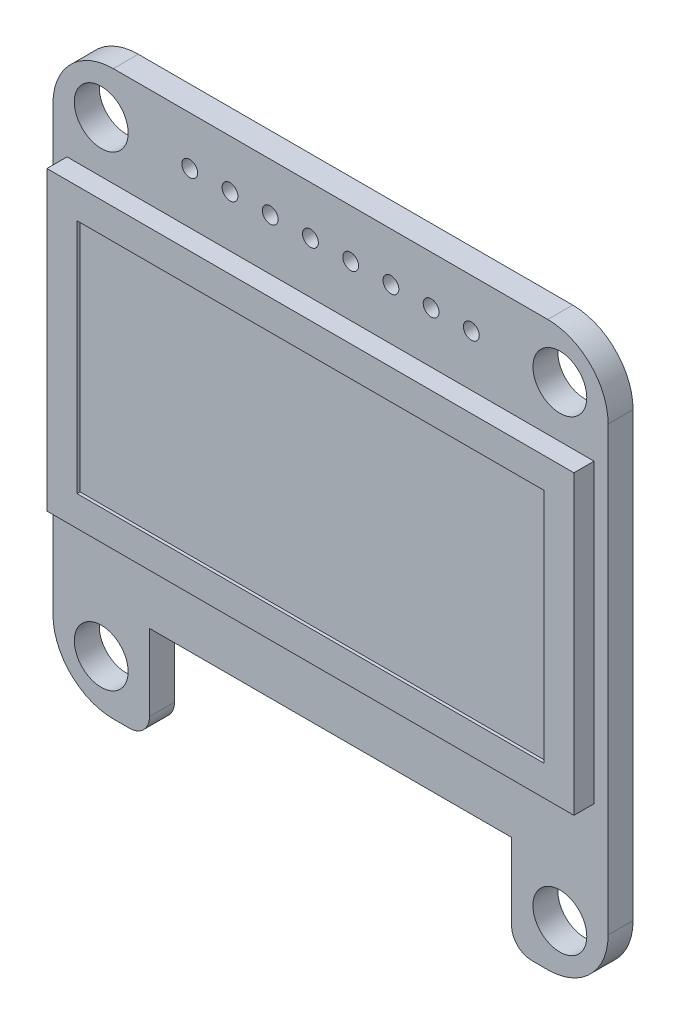
SolidWorks part; units mm, degrees
material "A-Glass Fiber"
ref_plane "Front Plane" through (0, 0, 0) normal (0, 0, 1) x (1, 0, 0)
ref_plane "Top Plane" through (0, 0, 0) normal (0, 1, 0) x (1, 0, 0)
ref_plane "Right Plane" through (0, 0, 0) normal (1, 0, 0) x (0, 0, -1)
sketch "Sketch2" plane through (0, 0, 0) normal (0, 0, 1) x (1, 0, 0)
  line L1 (-3.048, 32.512) -> (32.004, 32.512)
  line L2 (-3.048, 32.512) -> (-3.048, -3.048)
  line L3 (-3.048, -3.048) -> (32.004, -3.048)
  line L4 (32.004, 32.512) -> (32.004, -3.048)
  line L5 (3.048, -3.048) -> (25.908, -3.048)
  line L6 (3.048, -3.048) -> (3.048, 3.048)
  line L7 (3.048, 3.048) -> (25.908, 3.048)
  line L8 (25.908, -3.048) -> (25.908, 3.048)
  circle A0 centre (0, 0) radius 1.6002
  circle A2 centre (28.956, 0) radius 1.6002
  circle A3 centre (0, 29.464) radius 1.6002
  circle A4 centre (28.956, 29.464) radius 1.6002
  circle A5 centre (15.748, 29.464) radius 0.5
  circle A6 centre (18.288, 29.464) radius 0.5
  circle A7 centre (20.828, 29.464) radius 0.5
  circle A8 centre (23.368, 29.464) radius 0.5
  circle A9 centre (13.208, 29.464) radius 0.5
  circle A10 centre (10.668, 29.464) radius 0.5
  circle A11 centre (8.128, 29.464) radius 0.5
  circle A12 centre (5.588, 29.464) radius 0.5
  point P19 (14.478, 32.512)
  point P22 (0, 0)
  point P23 (17.5212, 29.464)
  point P26 (19.3342, 29.464)
  point P29 (20.8714, 29.464)
  point P32 (0, 0)
  point P33 (0, 0)
  point P34 (0, 0)
  point P35 (12.5156, 29.2129)
  point P36 (13.698, 29.464)
  point P39 (12.1214, 29.464)
  point P42 (0, 0)
  point P43 (10.2296, 29.464)
  point P46 (8.1406, 29.464)
  point P47 (0, 0)
  point P48 (0, 0)
  point P49 (0, 0)
  dimension "D1" = 28.956
  dimension "D2" = 29.464
  dimension "D10" = 1.27
  dimension "D3" = 35.052
  dimension "D4" = 35.56
  dimension "D5" = 3.048
  dimension "D6" = 3.048
  dimension "D7" = 6.096
  dimension "D8" = 22.86
  dimension "D9" = 6.096
  dimension "D11" = 2.54
  dimension "D12" = 2.54
  dimension "D13" = 2.54
  dimension "D14" = 2.54
  dimension "D15" = 2.54
  dimension "D16" = 2.54
  dimension "D17" = 2.54
extrude "Boss-Extrude1" add sketch "Sketch2" along normal blind 1.5748 contours L2 L3 L4 L1
extrude "Cut-Extrude4" cut sketch "Sketch2<8>" against normal blind 1.5748 from surface contours L7 L8 L5 L6 starting at face at (14.478, 14.732, 1.5748)
sketch "Sketch2<8>" plane through (0, 0, 0) normal (0, 0, 1) x (1, 0, 0) same geometry as "Sketch2"
hole_wizard "M3 Clearance Hole1" positions "Sketch6" profile "Sketch7" hole size "M3" standard "ANSI Metric" end condition through all
sketch "Sketch6" plane through (0, 0, 1.5748) normal (0, 0, 1) x (1, 0, 0)
  point P0 (0, 29.464)
  point P3 (0, 0)
  point P6 (28.956, 0)
  point P9 (28.956, 29.464)
sketch "Sketch7" plane through (0, 29.464, 1.5748) normal (1, 0, 0) x (0, -1, 0)
  line L0 (0, 0) -> (0, 1.5748)
  line L1 (0, 1.5748) -> (1.7, 1.5748)
  line L2 (1.7, 1.5748) -> (1.7, 0)
  line L5 (1.7, 0) -> (0, 0)
  line L11 (0, -6.35) -> (0, 107.95) construction
  dimension "Thru Hole Dia." = 3.4
  dimension "Thru Hole Depth" = 1.5748
hole_wizard "Ø1.0 (1) Diameter Hole1" positions "Sketch8" profile "Sketch9" hole size "Ø1.0" standard "ANSI Metric" end condition through all
sketch "Sketch8" plane through (0, 0, 1.5748) normal (0, 0, 1) x (1, 0, 0)
  point P0 (5.588, 29.464)
  point P3 (8.128, 29.464)
  point P6 (10.668, 29.464)
  point P9 (13.208, 29.464)
  point P12 (15.748, 29.464)
  point P15 (18.288, 29.464)
  point P18 (20.828, 29.464)
  point P21 (23.368, 29.464)
sketch "Sketch9" plane through (5.588, 29.464, 1.5748) normal (1, 0, 0) x (0, -1, 0)
  line L0 (0, 0) -> (0, 1.5748)
  line L1 (0, 1.5748) -> (0.5, 1.5748)
  line L2 (0.5, 1.5748) -> (0.5, 0)
  line L5 (0.5, 0) -> (0, 0)
  line L11 (0, -6.35) -> (0, 107.95) construction
  dimension "Thru Hole Dia." = 1
  dimension "Thru Hole Depth" = 1.5748
fillet "Fillet2" radius 3.81 4 edges at (-3.048, -3.048, 0.7874) (32.004, -3.048, 0.7874) (32.004, 32.512, 0.7874) (-3.048, 32.512, 0.7874)
fillet "Fillet3" radius 1.27 2 edges at (3.048, -3.048, 0.7874) (25.908, -3.048, 0.7874)
sketch "Sketch10" plane through (0, 0, 1.5748) normal (0, 0, 1) x (1, 0, 0)
  line L0 (-3.048, 32.512) -> (-3.048, -3.048) construction
  line L1 (29.21, 24.3191) -> (-0.254, 24.3191)
  line L2 (29.21, 24.3191) -> (29.21, 9.398)
  line L3 (29.21, 9.398) -> (-0.254, 9.398)
  line L4 (-0.254, 24.3191) -> (-0.254, 9.398)
  line L5 (31.115, 26.2241) -> (-2.159, 26.2241)
  line L6 (-2.159, 26.2241) -> (-2.159, 7.493)
  line L7 (31.115, 7.493) -> (-2.159, 7.493)
  line L8 (31.115, 26.2241) -> (31.115, 7.493)
  dimension "D1" = 32.258
  dimension "D2" = 29.464
  dimension "D3" = 6.35
  dimension "D4" = 1.905
extrude "Boss-Extrude2" add sketch "Sketch10" along normal blind 1.27 contours L5 L6 L7 L8
sketch "Sketch11" plane through (0, 0, 2.8448) normal (0, 0, 1) x (1, 0, 0)
  line L1 (-0.254, 24.3191) -> (29.21, 24.3191)
  line L2 (-0.254, 24.3191) -> (-0.254, 9.398)
  line L3 (-0.254, 9.398) -> (29.21, 9.398)
  line L4 (29.21, 24.3191) -> (29.21, 9.398)
extrude "Cut-Extrude5" cut sketch "Sketch11" against normal blind 0.1905
